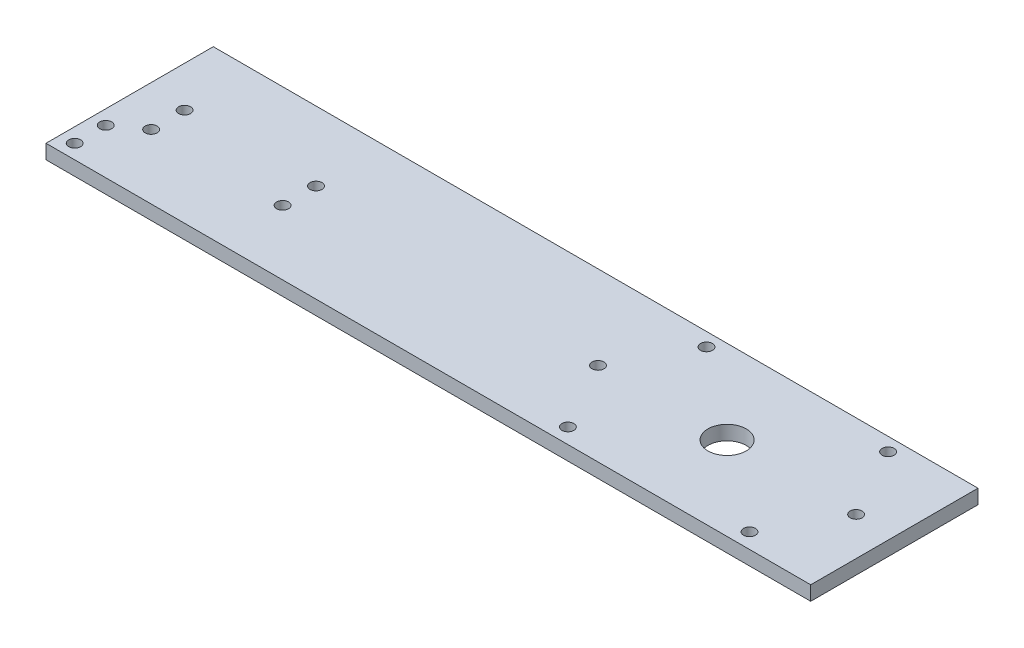
SolidWorks part; units mm, degrees
ref_plane "Front Plane" through (0, 0, 0) normal (0, 0, 1) x (1, 0, 0)
ref_plane "Top Plane" through (0, 0, 0) normal (0, 1, 0) x (1, 0, 0)
ref_plane "Right Plane" through (0, 0, 0) normal (1, 0, 0) x (0, 0, -1)
sketch "Sketch1" plane through (0, 0, 0) normal (0, 1, 0) x (1, 0, 0)
  line L0 (25, 13.2344) -> (25, -3.2344) construction
  line L1 (-100, 22.5) -> (60, 22.5)
  line L2 (-100, 22.5) -> (-100, -12.5)
  line L3 (-100, -12.5) -> (60, -12.5)
  line L4 (60, 22.5) -> (60, -12.5)
  line L5 (25, -1) -> (25, 11) construction
  line L6 (-10, -1) -> (60, -1)
  line L7 (-10, -1) -> (-10, 11)
  line L8 (-10, 11) -> (60, 11)
  line L9 (60, -1) -> (60, 11)
  line L10 (-10, -1) -> (60, 11) construction
  line L11 (-10, 11) -> (60, -1) construction
  circle A4 centre (25, 5) radius 4
  circle A5 centre (52, 5) radius 1.25
  circle A6 centre (-2, 5) radius 1.25
  circle A7 centre (-97, -9.5) radius 1.25
  circle A8 centre (-97, -3) radius 1.25
  circle A9 centre (-91.5, 8) radius 1.25
  circle A10 centre (-64, 8) radius 1.25
  circle A11 centre (-64, 1) radius 1.25
  circle A12 centre (-91.5, 1) radius 1.25
  point P0 (0, 0)
  point P25 (0, 0)
  dimension "D3" = 2.5
  dimension "D4" = 35
  dimension "D5" = 2.5
  dimension "D9" = 2.5
  dimension "D13" = 2.5
  dimension "D2" = 8
  dimension "D19" = 125
  dimension "D21" = 6
  dimension "D22" = 6
  dimension "D1" = 35
  dimension "D6" = 8
  dimension "D7" = 70
  dimension "D8" = 12
  dimension "D10" = 3
  dimension "D11" = 6.5
  dimension "D12" = 3
  dimension "D14" = 14.5
  dimension "D15" = 8.5
  dimension "D18" = 27.5
  dimension "D20" = 11.5
  dimension "D16" = 2
  dimension "D17" = 2
extrude "Boss-Extrude1" add sketch "Sketch1" along normal blind 3 contours L7 L8 L4 L1 L2 L3 L6 | L8 L7 L6 L4 A4 A5 A6 region at (-27.5911, 0, -5.0254) region at (59.2898, 0, -5)
sketch "Sketch2" plane through (0, 0, 0) normal (0, 0, 1) x (1, 0, 0)
  line L0 (-94.5, 33) -> (-94.5, -17) construction
  line L1 (-92, 33) -> (-92, -17)
  line L2 (-97, 33) -> (-97, -17)
  line L3 (-89, 33) -> (-89, -17)
  line L4 (-100, 33) -> (-100, -17)
  line L5 (-100, 3) -> (-100, 0) construction
  line L7 (-94, 6.4998) -> (-61.5, 6.4998)
  line L8 (-94, 6.4998) -> (-94, -3.3981)
  line L9 (-94, -3.3981) -> (-61.5, -3.3981)
  line L10 (-61.5, 6.4998) -> (-61.5, -3.3981)
  arc A0 (-92, 33) -> (-97, 33) centre (-94.5, 33) ccw
  arc A1 (-97, -17) -> (-92, -17) centre (-94.5, -17) ccw
  arc A2 (-100, -17) -> (-89, -17) centre (-94.5, -17) ccw
  arc A3 (-89, 33) -> (-100, 33) centre (-94.5, 33) ccw
  point P2 (-94.5, 8)
  dimension "D4" = 5.5
  dimension "D1" = 3
  dimension "D2" = 3
  dimension "D3" = 5
  dimension "D5" = 50
  dimension "D6" = 50
  dimension "D7" = 6
  dimension "D8" = 32.5
extrude "Cut-Extrude3" [suppressed] cut sketch "Sketch2" along normal up to surface (9 mm away) from offset 3.5 contours L1 L9 L3 L7 | L10 L7 L3 L9 | L8 L9 L1 L7 up to face at (-20, 1.5, 12.5)
ref_plane "Plane3" through (0, 3, 0) normal (0, -1, 0) x (-1, 0, 0)
sketch "Sketch3" plane through (0, 3, 0) normal (0, -1, 0) x (-1, 0, 0)
  line L0 (-60, -12.5) -> (2, -12.5)
  line L2 (2, 5) -> (2, -12.5) construction
  line L3 (-52, 5) -> (-52, -12.5) construction
  line L5 (-47.0043, 22.7064) -> (-47.0043, -12.2936)
  line L6 (-37.5, -12.5) -> (25.1934, -12.5) construction
  line L7 (2, -12.5) -> (2, 22.5)
  line L8 (100, 22.5) -> (-60, 22.5) construction
  line L9 (2, 22.5) -> (-60, 22.5)
  line L10 (-3, 22.5) -> (-3, -12.5)
  line L11 (-47.0043, 22.7064) -> (-3, 22.5)
  line L12 (-47.0043, -12.2936) -> (-3, -12.5)
  circle A4 centre (-44, -9.3076) radius 1.25
  circle A5 centre (-6, -9.3076) radius 1.25
  circle A6 centre (-6, 19.6924) radius 1.25
  circle A7 centre (-44, 19.6924) radius 1.25
  point P14 (-47.0043, 5.2064)
  dimension "D3" = 35
  dimension "D4" = 5
  dimension "D8" = 8
  dimension "D14" = 2.5
  dimension "D1" = 54
  dimension "D2" = 5
  dimension "D5" = 62
  dimension "D6" = 54
  dimension "D7" = 44.0043
  dimension "D9" = 3.0043
  dimension "D10" = 3
  dimension "D13" = 3
  dimension "D11" = 2
  dimension "D12" = 2
extrude "Cut-Extrude7" cut sketch "Sketch3" along normal blind 10 contours A4 | A7 | A6 | A5 region at (44, 3, 9.3076)
